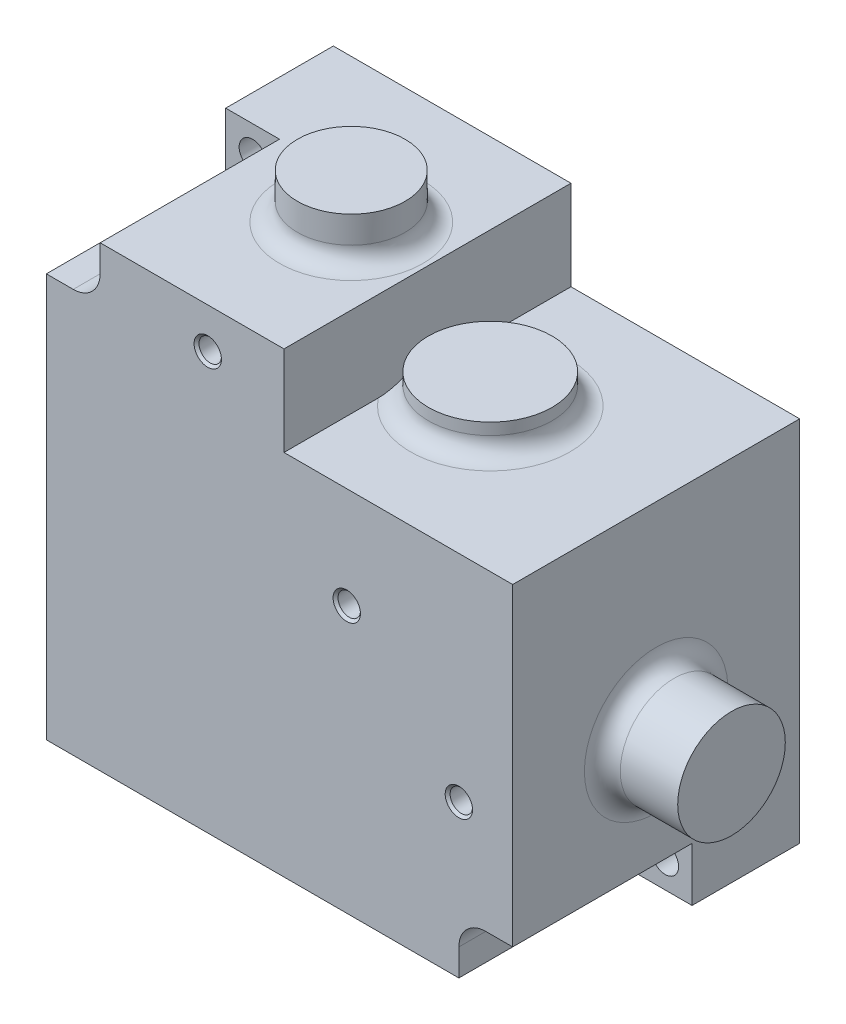
SolidWorks part; units mm, degrees
ref_plane "Front Plane" through (0, 0, 0) normal (0, 0, 1) x (1, 0, 0)
ref_plane "Top Plane" through (0, 0, 0) normal (0, 1, 0) x (1, 0, 0)
ref_plane "Right Plane" through (0, 0, 0) normal (1, 0, 0) x (0, 0, -1)
sketch "Sketch1" plane through (0, 0, 0) normal (0, 0, 1) x (1, 0, 0)
  line L0 (-25.5, 51) -> (-25.5, 41)
  line L1 (0, 0) -> (-52, 0)
  line L2 (0, 0) -> (0, 41)
  line L3 (-25.5, 51) -> (-52, 51)
  line L4 (-52, 0) -> (-52, 51)
  line L5 (-25.5, 41) -> (0, 41)
  dimension "D1" = 51
  dimension "D2" = 52
  dimension "D3" = 26.5
  dimension "D4" = 41
extrude "Boss-Extrude1" add sketch "Sketch1" along normal blind 32
sketch "Sketch2" plane through (-52, 0, 0) normal (-1, 0, 0) x (0, 0, 1)
  line L0 (0, 51) -> (0, 0) construction
  line L1 (32, 0) -> (0, 0) construction
  circle A0 centre (16, 16.75) radius 9.5
  dimension "D3" = 19
  dimension "D1" = 16
  dimension "D2" = 16.75
extrude "Cut-Extrude1" cut sketch "Sketch2" against normal blind 0.3 contours A0
sketch "Sketch3" plane through (-51.7, 0, 0) normal (-1, 0, 0) x (0, 0, 1)
  circle A0 centre (16, 16.75) radius 4
  dimension "D1" = 8
extrude "Cut-Extrude2" cut sketch "Sketch3" against normal blind 5
sketch "Sketch4" plane through (0, 0, 32) normal (0, 0, 1) x (1, 0, 0)
  line L0 (-6, 3) -> (-6, 0)
  line L1 (-52, 0) -> (0, 0) construction
  line L2 (-3, 6) -> (0, 6)
  line L3 (0, 0) -> (0, 41) construction
  line L4 (-52, 45) -> (-49, 45)
  line L5 (-52, 51) -> (-52, 0) construction
  line L6 (-46, 48) -> (-46, 51)
  line L7 (-25.5, 51) -> (-52, 51) construction
  line L8 (-46, 51) -> (-52, 51)
  line L9 (-52, 51) -> (-52, 45)
  line L10 (-6, 0) -> (0, 0)
  line L11 (0, 0) -> (0, 6)
  arc A0 (-3, 6) -> (-6, 3) centre (-3, 3) ccw
  arc A1 (-46, 48) -> (-49, 45) centre (-49, 48) cw
  dimension "D3" = 6
  dimension "D1" = 6
  dimension "D2" = 6
extrude "Cut-Extrude3" cut sketch "Sketch4" against normal offset from surface (20 mm away) 12 up to face at (-25.8333, 30.6667, 0)
sketch "Sketch5" plane through (0, 0, 12) normal (0, 0, 1) x (1, 0, 0)
  circle A0 centre (-3, 3) radius 1.5
  circle A1 centre (-49, 48) radius 1.5
  dimension "D1" = 3
extrude "Cut-Extrude4" cut sketch "Sketch5" against normal through all both and the other way through all
hole_wizard "M3 Tapped Hole1" positions "Sketch7" profile "Sketch8" tap size "M3" standard "DIN"
sketch "Sketch7" plane through (0, 0, 0) normal (0, 0, -1) x (-1, 0, 0)
  line L0 (52, 51) -> (52, 0) construction
  line L1 (0, 0) -> (0, 41) construction
  line L2 (52, 0) -> (0, 0) construction
  point P0 (7, 31)
  point P2 (7, 11)
  point P4 (47, 31)
  dimension "D1" = 5
  dimension "D2" = 7
  dimension "D3" = 31
  dimension "D4" = 11
cosmetic thread "Hole Thread1" parameters "D1"=6, "D2"=3
cosmetic thread "Hole Thread2" parameters "D1"=6, "D2"=3
cosmetic thread "Hole Thread3" parameters "D1"=6, "D2"=3
sketch "Sketch8" plane through (-7, 31, 0) normal (1, 0, 0) x (0, 1, 0)
  line L0 (0, 0) -> (0, 8.2511)
  line L1 (0, 8.2511) -> (1.25, 7.5)
  line L2 (1.25, 7.5) -> (1.25, 0.275)
  line L3 (1.25, 0.275) -> (1.525, 0)
  line L5 (1.525, 0) -> (0, 0)
  line L6 (-1.25, 0.275) -> (-1.525, 0) construction
  line L10 (0, 8.2511) -> (-1.25, 7.5) construction
  line L11 (0, -6.35) -> (0, 107.95) construction
  dimension "Tap Drill Dia." = 2.5
  dimension "Tap Drill Depth" = 7.5
  dimension "Near C'Sink Dia." = 3.05
  dimension "Near C'Sink Angle" = 90
  dimension "Drill Angle" = 118
sketch "Sketch9" plane through (0, 0, 0) normal (0, -1, 0) x (1, 0, 0)
  line L0 (-52, 32) -> (-52, 0) construction
  line L1 (-48.2, 3.6) -> (-8.4, 3.6)
  line L2 (-48.2, 3.6) -> (-48.2, 27)
  line L3 (-48.2, 27) -> (-8.4, 27)
  line L4 (-8.4, 3.6) -> (-8.4, 27)
  line L5 (0, 12) -> (0, 0) construction
  line L6 (-52, 0) -> (0, 0) construction
  line L7 (-52, 32) -> (-6, 32) construction
  dimension "D1" = 3.8
  dimension "D2" = 8.4
  dimension "D3" = 3.6
  dimension "D4" = 5
extrude "Boss-Extrude2" add sketch "Sketch9" along normal blind 1.1
sketch "Sketch10" plane through (0, 0, 0) normal (1, 0, 0) x (0, 0, -1)
  line L0 (0, 0) -> (0, 41) construction
  circle A0 centre (-16, 18.9454) radius 6
  dimension "D1" = 12
  dimension "D2" = 16
extrude "Boss-Extrude3" add sketch "Sketch10" along normal blind 8.4
sketch "Sketch11" plane through (0, 51, 0) normal (0, 1, 0) x (1, 0, 0)
  line L0 (-25.5, 0) -> (-52, 0) construction
  line L1 (-52, -12) -> (-52, 0) construction
  circle A0 centre (-34, -16) radius 6
  dimension "D1" = 12
  dimension "D2" = 16
  dimension "D3" = 18
extrude "Boss-Extrude4" add sketch "Sketch11" along normal blind 5
sketch "Sketch12" plane through (0, 41, 0) normal (0, 1, 0) x (1, 0, 0)
  line L0 (0, -32) -> (0, 0) construction
  line L1 (0, 0) -> (-25.5, 0) construction
  circle A0 centre (-18.5, -16) radius 6.8949
  dimension "D1" = 18.5
  dimension "D2" = 16
extrude "Boss-Extrude5" add sketch "Sketch12" along normal blind 3.3
fillet "Fillet1" radius 2 3 edges at (0, 18.9454, 22) (-34, 51, 10) (-18.5, 41, 9.1051)
hole_wizard "M3 Tapped Hole2" positions "Sketch13" profile "Sketch14" tap size "M3" standard "DIN"
sketch "Sketch13" plane through (0, 0, 32) normal (0, 0, 1) x (1, 0, 0)
  line L0 (-52, 45) -> (-52, 0) construction
  line L1 (-25.5, 51) -> (-46, 51) construction
  line L2 (-8.4, 0) -> (-48.2, 0) construction
  line L3 (0, 6) -> (0, 41) construction
  line L4 (-52, 0) -> (-6, 0) construction
  point P0 (-34, 46.5)
  point P2 (-18.5, 29.7)
  point P4 (-6, 17)
  dimension "D1" = 18
  dimension "D2" = 4.5
  dimension "D3" = 33.5
  dimension "D4" = 29.7
  dimension "D5" = 6
  dimension "D6" = 17
sketch "Sketch14" plane through (-34, 46.5, 32) normal (1, 0, 0) x (0, -1, 0)
  line L0 (0, 0) -> (0, 8.2511)
  line L1 (0, 8.2511) -> (1.25, 7.5)
  line L2 (1.25, 7.5) -> (1.25, 0.275)
  line L3 (1.25, 0.275) -> (1.525, 0)
  line L5 (1.525, 0) -> (0, 0)
  line L6 (-1.25, 0.275) -> (-1.525, 0) construction
  line L10 (0, 8.2511) -> (-1.25, 7.5) construction
  line L11 (0, -6.35) -> (0, 107.95) construction
  dimension "Tap Drill Dia." = 2.5
  dimension "Tap Drill Depth" = 7.5
  dimension "Near C'Sink Dia." = 3.05
  dimension "Near C'Sink Angle" = 90
  dimension "Drill Angle" = 118
cosmetic thread "Hole Thread4" parameters "D1"=6, "D2"=3
cosmetic thread "Hole Thread5" parameters "D1"=6, "D2"=3
cosmetic thread "Hole Thread6" parameters "D1"=6, "D2"=3
